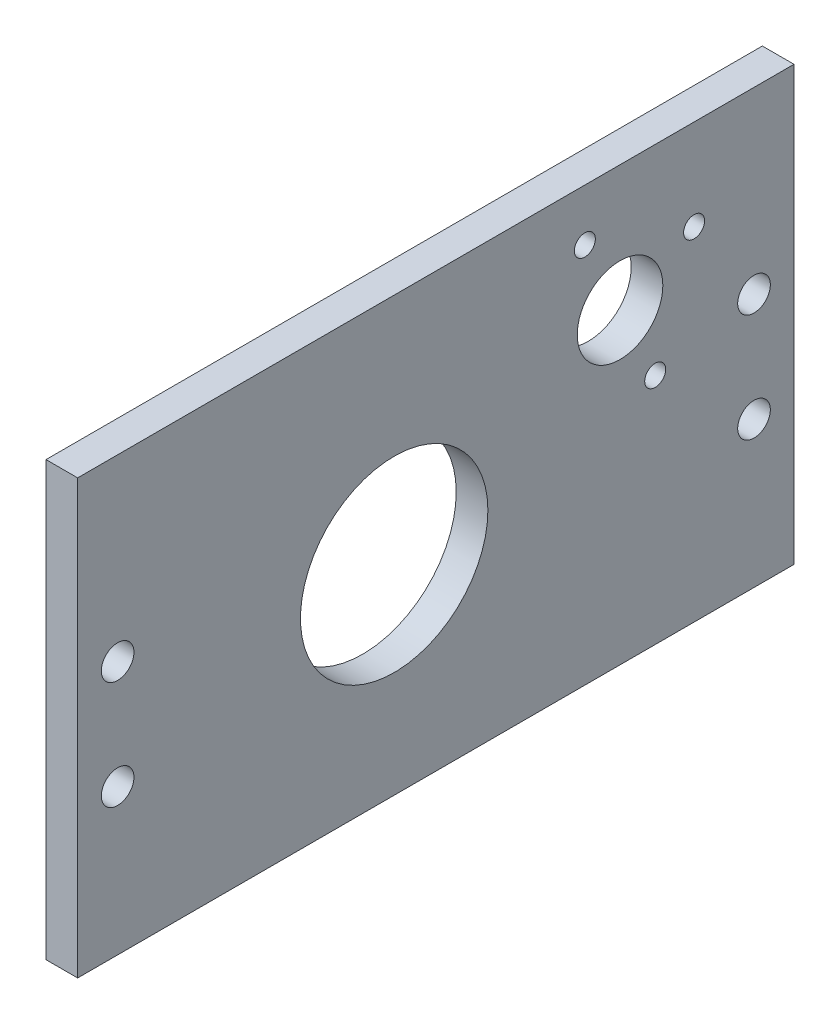
SolidWorks part; units mm, degrees
material "6061-T6 (SS)"
ref_plane "Front Plane" through (0, 0, 0) normal (0, 0, 1) x (1, 0, 0)
ref_plane "Top Plane" through (0, 0, 0) normal (0, 1, 0) x (1, 0, 0)
ref_plane "Right Plane" through (0, 0, 0) normal (1, 0, 0) x (0, 0, -1)
sketch "Sketch2" plane through (0, 0, 0) normal (1, 0, 0) x (0, 0, -1)
  line L0 (54.864, 8.255) -> (54.864, -8.255) construction
  line L1 (-48.26, 35.56) -> (60.96, 35.56)
  line L2 (-48.26, 35.56) -> (-48.26, -30.48)
  line L3 (-48.26, -30.48) -> (60.96, -30.48)
  line L4 (60.96, 35.56) -> (60.96, -30.48)
  line L5 (23.146, 10.9965) -> (39.8007, 5.0699) construction
  line L6 (39.8007, 5.0699) -> (45.7272, 21.7245) construction
  line L7 (45.7272, 21.7245) -> (29.0726, 27.6511) construction
  line L8 (29.0726, 27.6511) -> (23.146, 10.9965) construction
  line L9 (-42.164, 8.255) -> (-42.164, -8.255) construction
  line L10 (0, 0) -> (34.4366, 16.3605) construction
  line L11 (60.96, 13.335) -> (48.768, 13.335) construction
  line L12 (60.96, 13.335) -> (60.96, -13.335) construction
  line L13 (60.96, -13.335) -> (48.768, -13.335) construction
  line L14 (48.768, 13.335) -> (48.768, -13.335) construction
  circle A0 centre (0, 0) radius 14.2875
  circle A1 centre (0, 0) radius 33.0327 construction
  circle A2 centre (34.4366, 16.3605) radius 5.0927 construction
  circle A3 centre (34.4366, 16.3605) radius 17.5 construction
  circle A4 centre (34.4366, 16.3605) radius 6.525
  circle A5 centre (34.4366, 16.3605) radius 12.5 construction
  circle A6 centre (54.864, 8.255) radius 2.4892
  circle A7 centre (54.864, -8.255) radius 2.4892
  circle A8 centre (-42.164, 8.255) radius 2.4892
  circle A9 centre (-42.164, -8.255) radius 2.4892
  circle A10 centre (82.55, 0) radius 19.9136 construction
  circle A11 centre (45.7272, 21.7245) radius 2.75 construction
  circle A12 centre (39.8007, 5.0699) radius 2.75 construction
  circle A13 centre (54.864, 8.255) radius 3.9687 construction
  point P18 (54.864, 0)
  point P22 (60.96, 2.54)
  point P31 (0, 0)
  point P32 (0, 0)
  point P33 (34.4366, 33.8605)
  dimension "D1" = 28.575
  dimension "D2" = 66.0654
  dimension "D3" = 10.1854
  dimension "D4" = 35
  dimension "D9" = 13.05
  dimension "D10" = 25
  dimension "D12" = 4.9784
  dimension "D16" = 39.8272
  dimension "D20" = 5.5
  dimension "D22" = 7.9375
  dimension "D5" = 30.48
  dimension "D6" = 66.04
  dimension "D7" = 109.22
  dimension "D8" = 48.26
  dimension "D11" = 16.51
  dimension "D13" = 6.096
  dimension "D14" = 6.096
  dimension "D15" = 82.55
  dimension "D17" = 12.192
  dimension "D18" = 5.08
  dimension "D19" = 5.08
  dimension "D21" = 21.9767
extrude "Boss-Extrude1" add sketch "Sketch2" against normal blind 4.826
hole_wizard "M3 Clearance Hole1" positions "Sketch3" profile "Sketch4" hole size "M3" standard "ANSI Metric" end condition through all
sketch "Sketch3" plane through (0, 0, 0) normal (1, 0, 0) x (0, 0, -1)
  point P0 (39.8007, 5.0699)
  point P3 (29.0726, 27.6511)
  point P9 (45.7272, 21.7245)
sketch "Sketch4" plane through (0, 5.0699, -39.8007) normal (0, 1, 0) x (0, 0, -1)
  line L0 (0, 0) -> (0, 4.826)
  line L1 (0, 4.826) -> (1.6, 4.826)
  line L2 (1.6, 4.826) -> (1.6, 0)
  line L5 (1.6, 0) -> (0, 0)
  line L11 (0, -6.35) -> (0, 107.95) construction
  dimension "Thru Hole Dia." = 3.2
  dimension "Thru Hole Depth" = 4.826
